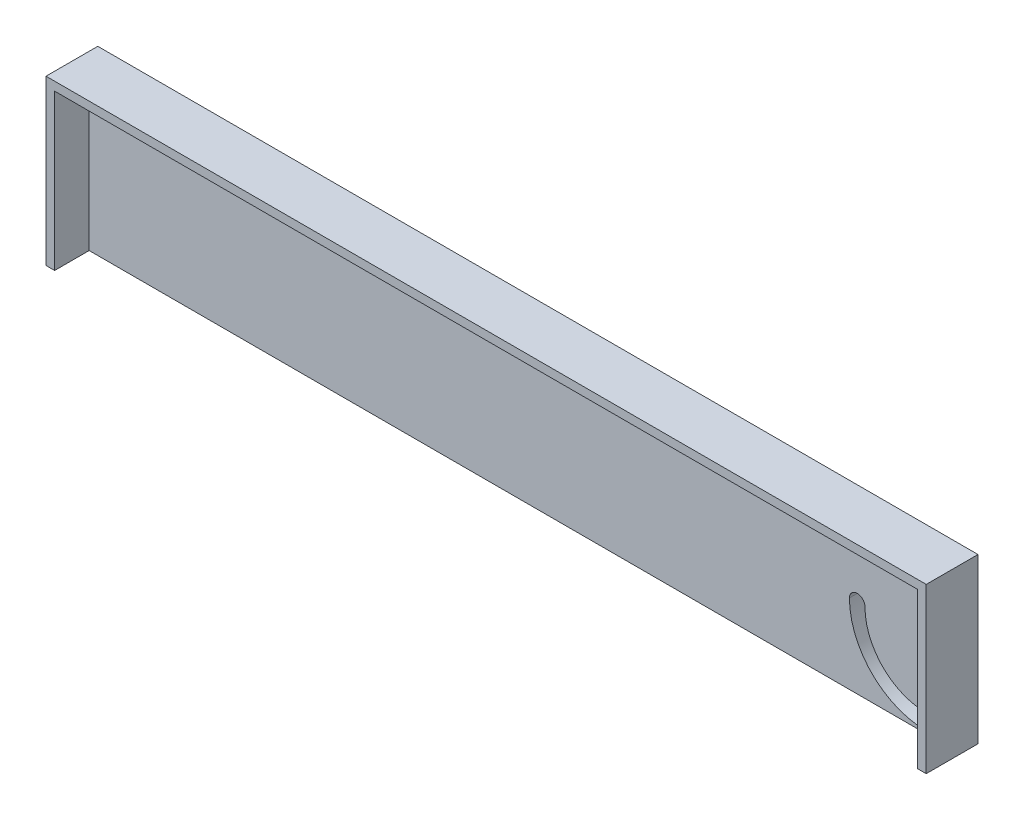
SolidWorks part; units mm, degrees
ref_plane "Front Plane" through (0, 0, 0) normal (0, 0, 1) x (1, 0, 0)
ref_plane "Top Plane" through (0, 0, 0) normal (0, 1, 0) x (1, 0, 0)
ref_plane "Right Plane" through (0, 0, 0) normal (1, 0, 0) x (0, 0, -1)
sketch "Sketch1" plane through (0, 0, 0) normal (0, 0, 1) x (1, 0, 0)
  line L0 (0, -100) -> (5, -95)
  line L1 (0, 0) -> (510, 0)
  line L2 (0, 0) -> (0, -100)
  line L3 (0, -100) -> (510, -100)
  line L4 (510, 0) -> (510, -100)
  line L5 (5, -5) -> (505, -5)
  line L6 (5, -5) -> (5, -95)
  line L7 (5, -95) -> (505, -95)
  line L8 (505, -5) -> (505, -95)
  line L9 (510, -100) -> (505, -95)
  dimension "D1" = 510
  dimension "D2" = 500
  dimension "D3" = 100
  dimension "D4" = 90
  dimension "D5" = 5
  dimension "D6" = 5
extrude "Boss-Extrude1" add sketch "Sketch1" along normal blind 20 contours L8 L5 L6 L7 | L1 L4 L3 L2 region at (255, -50, 0)
sketch "Sketch2" plane through (0, 0, 0) normal (0, 0, 1) x (1, 0, 0)
  line L1 (0, 0) -> (510, 0)
  line L2 (0, 0) -> (0, -100)
  line L3 (0, -100) -> (510, -100)
  line L4 (510, 0) -> (510, -100)
extrude "Boss-Extrude2" add sketch "Sketch2" against normal blind 10
sketch "Sketch3" plane through (0, 0, 0) normal (0, 0, 1) x (1, 0, 0)
  line L2 (505, -5) -> (505, -95) construction
  line L3 (5, -5) -> (505, -5) construction
  circle A2 centre (490, -49) radius 4.5
  arc A15 (490, -93.5) -> (490, -84.5) centre (490, -89) ccw
  arc A16 (490, -13.5) -> (490, -4.5) centre (490, -9) ccw
  arc A20 (454.5, -49) -> (445.5, -49) centre (450, -49) ccw
  arc A21 (490, -93.5) -> (445.5, -49) centre (490, -49) cw
  arc A22 (490, -84.5) -> (454.5, -49) centre (490, -49) cw
  point P6 (0, 0)
  point P7 (0, 0)
  point P17 (0, 0)
  dimension "D3" = 44
  dimension "D6" = 9
  dimension "D5" = 9
  dimension "D7" = 40
  dimension "D8" = 9
  dimension "D9" = 9
  dimension "D2" = 15
  dimension "D10" = 40
extrude "Cut-Extrude1" cut sketch "Sketch3" against normal blind 1070 contours A15 A22 A20 A21 | A2 | A15 A22 A16 A21 | A20 region at (459.0237, -79.9763, 0)
sketch "Sketch4" plane through (0, 0, 0) normal (0, 0, 1) x (1, 0, 0)
  line L0 (0, 0) -> (0, -100) construction
  line L1 (0, -95) -> (510, -95)
  line L2 (0, -95) -> (0, -100)
  line L3 (0, -100) -> (510, -100)
  line L4 (510, -95) -> (510, -100)
  line L5 (5, -95) -> (505, -95) construction
extrude "Cut-Extrude2" cut sketch "Sketch4" against normal mid plane 40
sketch "Sketch5" plane through (0, 0, 0) normal (0, 0, 1) x (1, 0, 0)
  arc A0 (490, -89) -> (450, -49) centre (490, -49) cw
